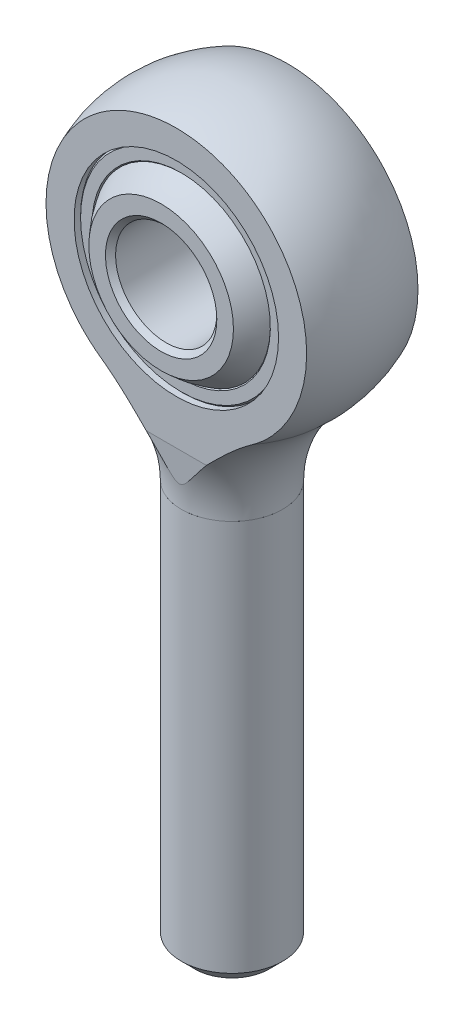
SolidWorks part; units mm, degrees
ref_plane "Front" through (0, 0, 0) normal (0, 0, 1) x (1, 0, 0)
ref_plane "Top" through (0, 0, 0) normal (0, 1, 0) x (1, 0, 0)
ref_plane "Right" through (0, 0, 0) normal (1, 0, 0) x (0, 0, -1)
sketch "Sketch1" plane through (0, 0, 0) normal (0, 0, 1) x (1, 0, 0)
  line L0 (0, 0) -> (0, -31.75)
  line L1 (0, -31.75) -> (3.9688, -31.75)
  line L2 (3.9688, -31.75) -> (3.9688, 0)
  line L3 (3.9688, 0) -> (0, 0)
  line L5 (0, 26.9875) -> (0, 0) construction
  line L6 (0, 26.9875) -> (11.1125, 26.9875) construction
  line L7 (11.1125, 26.9875) -> (11.1125, 15.875) construction
  line L8 (-3.9687, -31.75) -> (-3.9687, 0) construction
  arc A0 (7.3698, 7.558) -> (0, 26.9875) centre (0, 15.875) ccw construction
  circle A1 centre (0, 15.875) radius 3.9688 construction
  circle A2 centre (0, 15.875) radius 7.9375 construction
  circle A3 centre (0, 15.875) radius 8.0169 construction
  arc A4 (3.9688, 0) -> (7.3698, 7.558) centre (14.067, 0) cw construction
  point P16 (-3.9687, -24.6062)
  dimension "A" = 7.9375
  dimension "Ball Dia" = 15.875
  dimension "B" = 22.225
  dimension "D1" = 16.0337
  dimension "D" = 47.625
  dimension "E" = 31.75
  dimension "Thread Dia" = 7.9375
  dimension "D2" = 7.1438
revolve "Revolve1" add sketch "Sketch1" angle 360 about L5
sketch "Sketch12" [suppressed] plane through (0, -31.75, 0) normal (0, -1, 0) x (1, 0, 0)
  circle A1 centre (0, 0) radius 3.9688
  circle A2 centre (0, 0) radius 3.9688
  dimension "D1" = 0
chamfer "Chamfer2" distance 1.0583 angle 45 1 edges at (-3.9687, -31.75, 0)
sketch "Sketch4" plane through (0, 0, 0) normal (0, 0, 1) x (1, 0, 0)
  line L0 (3.9688, 0) -> (0, 0) construction
  line L2 (0, 26.9875) -> (0, 0) construction
  line L3 (3.9688, 0) -> (0, 0)
  line L5 (0, 26.9875) -> (0, 0)
  line L6 (0, 26.9875) -> (0, 29.5275) construction
  arc A0 (7.3698, 7.558) -> (0, 26.9875) centre (0, 15.875) ccw construction
  arc A1 (7.3698, 7.558) -> (0, 26.9875) centre (0, 15.875) ccw
  arc A2 (7.3698, 7.558) -> (3.9688, 0) centre (14.067, 0) ccw construction
  arc A3 (7.3698, 7.558) -> (3.9688, 0) centre (14.067, 0) ccw
  dimension "D1" = 2.54
revolve "Revolve2" add sketch "Sketch4" angle 360 about L6
sketch "Sketch5" plane through (0, 0, 0) normal (1, 0, 0) x (0, 0, -1)
  line L0 (4.3656, 26.9875) -> (11.1125, 26.9875)
  line L1 (-4.3656, 26.9875) -> (4.3656, 26.9875) construction
  line L2 (-4.3656, 26.9875) -> (-4.3656, 4.3656)
  line L3 (-3.9688, 0) -> (3.9688, 0) construction
  line L4 (4.3656, 26.9875) -> (4.3656, 4.3656)
  line L5 (11.1125, 26.9875) -> (11.1125, 0)
  line L6 (11.1125, 0) -> (3.9688, 0)
  line L7 (-3.9688, 0) -> (-11.1125, 0)
  line L8 (-11.1125, 0) -> (-11.1125, 26.9875)
  line L9 (-11.1125, 26.9875) -> (-4.3656, 26.9875)
  line L10 (3.9688, 0) -> (4.3656, 4.3656)
  line L11 (-3.9688, 0) -> (-4.3656, 4.3656)
  line L12 (-4.3656, 4.3656) -> (4.3656, 4.3656) construction
  line L13 (0, 0) -> (0, 4.3656) construction
  arc A0 (7.3698, 7.558) -> (-7.3698, 7.558) centre (0, 15.875) ccw construction
  dimension "F" = 8.7312
  dimension "D2" = 4.3656
  dimension "D1" = 7.9375
extrude "Cut-Extrude1" cut sketch "Sketch5" against normal through all and the other way through all
sketch "Sketch6" plane through (0, 0, 0) normal (0, 0, 1) x (1, 0, 0)
  circle A0 centre (0, 15.875) radius 8.0169 construction
  circle A1 centre (0, 15.875) radius 8.0169
extrude "Cut-Extrude2" cut sketch "Sketch6" against normal through all and the other way through all
sketch "Sketch7" plane through (0, 0, 0) normal (0, 0, 1) x (1, 0, 0)
  line L0 (0, 23.8125) -> (0, 7.9375)
  line L1 (0, 26.9875) -> (0, 0) construction
  line L2 (0, 0) -> (0, 7.9375) construction
  arc A0 (0, 7.9375) -> (0, 23.8125) centre (0, 15.875) ccw
  circle A1 centre (0, 15.875) radius 7.9375 construction
revolve "Revolve3" add sketch "Sketch7" angle 360 about L2
sketch "Sketch8" plane through (0, 0, 0) normal (1, 0, 0) x (0, 0, -1)
  line L0 (-4.3656, 26.9875) -> (4.3656, 26.9875) construction
  line L1 (-5.5562, 26.9875) -> (5.5562, 26.9875) construction
  line L2 (-5.5562, 26.9875) -> (-5.5563, 0)
  line L3 (-5.5563, 0) -> (5.5563, 0) construction
  line L4 (5.5562, 26.9875) -> (5.5563, 0)
  line L5 (5.5562, 26.9875) -> (11.1125, 26.9875)
  line L6 (11.1125, 26.9875) -> (11.1125, 0)
  line L7 (11.1125, 0) -> (5.5563, 0)
  line L8 (-5.5563, 0) -> (-11.1125, 0)
  line L9 (-11.1125, 0) -> (-11.1125, 26.9875)
  line L10 (-11.1125, 26.9875) -> (-5.5562, 26.9875)
  dimension "C" = 11.1125
extrude "Cut-Extrude3" cut sketch "Sketch8" against normal through all and the other way through all
sketch "Sketch10" plane through (0, 0, 0) normal (0, 0, 1) x (1, 0, 0)
  circle A0 centre (0, 15.875) radius 3.9688 construction
  circle A1 centre (0, 15.875) radius 3.9688
extrude "Cut-Extrude4" cut sketch "Sketch10" against normal through all and the other way through all
chamfer "Chamfer1" distance 0.3969 angle 45 2 edges at (3.9687, 15.875, -5.5562) (3.9687, 15.875, 5.5562)
sketch "Sketch14" plane through (0, 0, 0) normal (1, 0, 0) x (0, 0, -1)
  line L0 (-3.9846, 23.8919) -> (-3.9846, 22.7399)
  line L1 (-3.9846, 23.8919) -> (-1.6558, 23.8919)
  line L2 (-1.6558, 23.8919) -> (-1.6558, 23.6379)
  line L3 (3.9846, 22.7399) -> (3.9846, 23.8919)
  line L4 (3.9846, 23.8919) -> (1.6558, 23.8919)
  line L5 (1.6558, 23.8919) -> (1.6558, 23.6379)
  line L8 (-5.5562, 15.875) -> (5.5562, 15.875) construction
  line L9 (-5.5562, 21.5435) -> (-5.5562, 10.2065) construction
  line L10 (4.3656, 23.8919) -> (-4.3656, 23.8919) construction
  line L11 (-4.3656, 26.094) -> (-4.3656, 7.558) construction
  arc A1 (3.9846, 22.7399) -> (1.6558, 23.6379) centre (0, 15.875) ccw
  arc A2 (-1.6558, 23.6379) -> (-3.9846, 22.7399) centre (0, 15.875) ccw
  arc A3 (5.5562, 21.5435) -> (-5.5562, 21.5435) centre (0, 15.875) ccw construction
  dimension "D1" = 0.381
  dimension "D2" = 0.254
revolve "Revolve4" add sketch "Sketch14" angle 360 about L8
chamfer "Chamfer3" distance 0.127 angle 45 2 edges at (0, 7.8581, 3.9846) (0, 9.0101, 3.9846) first distance on face at (0, 7.8581, 3.9846) first distance on face at (0, 9.0101, 3.9846)
chamfer "Chamfer4" distance 0.127 angle 45 2 edges at (0, 9.0101, -3.9846) (0, 7.8581, -3.9846) first distance on face at (0, 9.0101, -3.9846) first distance on face at (0, 7.8581, -3.9846)
sketch "Sketch11" plane through (0, 0, 0) normal (1, 0, 0) x (0, 0, -1)
  line L0 (0, 15.875) -> (-5.5563, 16.5572) construction
  line L1 (4.3656, 15.875) -> (-4.3656, 15.875) construction
  line L2 (0, 15.875) -> (-5.5563, 15.1928) construction
  line L3 (0, 26.9875) -> (0, 0) construction
  line L4 (-5.5562, 26.9875) -> (-5.5563, 0) construction
  line L5 (0, 15.875) -> (0.0074, 15.875) construction
  dimension "Swivel" = 14
curve "Helix/Spiral1" [suppressed] pitch 1.0583 height 33.1248 turns 31.299 parameters "pitch"=1.0583
sketch "Sketch13" [suppressed] plane through (0, 0, 0) normal (1, 0, 0) x (0, 0, -1)
  line L0 (-3.9688, -32.676) -> (-3.9688, -31.75)
  line L1 (-3.9688, -31.75) -> (-3.2813, -32.1469)
  line L2 (-3.2813, -32.1469) -> (-3.2813, -32.2792)
  line L3 (-3.2813, -32.2792) -> (-3.9688, -32.676)
  line L4 (-3.2813, -32.213) -> (-3.9688, -32.213) construction
  line L5 (-3.625, -32.4776) -> (-3.625, -31.9484) construction
  line L6 (-3.9688, -31.75) -> (3.9688, -31.75) construction
  dimension "D1" = 0.1323
  dimension "D2" = 0.5292
  dimension "D3" = 60
sweep "Cut-Sweep1" [suppressed] cut profiles "Sketch13" path "Helix/Spiral1"
sketch "Sketch15" [suppressed] plane through (0, 0, 0) normal (0, -1, 0) x (1, 0, 0)
  arc A2 (0, -3.9688) -> (0, 3.9688) centre (0, 0) ccw
  arc A3 (0, 3.9688) -> (0, -3.9688) centre (0, 0) ccw
  arc A5 (0, 3.9688) -> (0, -3.9688) centre (0, 0) ccw
  arc A6 (0, -3.9688) -> (0, 3.9688) centre (0, 0) ccw
  dimension "D1" = 0
extrude "Boss-Extrude1" [suppressed] add sketch "Sketch15" along normal up to next draft 20
ref_axis "Center Axis 1" through (0, 15.875, -1.6345) along (0, 0, 1)
ref_axis "Center Axis 2" [suppressed] through (0, 29.9244, 0) along (0, -1, 0)
ref_axis "Axis1" through (0, 0, 0) along (0, -1, 0)
ref_point "Point2"
equation "\"D1@Sketch1\"=\"Ball Dia@Sketch1\"*1.01"
equation "\"D1@Chamfer1\"=\"A@Sketch1\"/20"
equation "\"D1@Sketch5\"=\"Thread Dia@Sketch1\""
equation "\"D2@Sketch5\"=\"F@Sketch5\"/2"
equation "\"D1@Sketch13\" = \"pitch@Helix/Spiral1\"*.125"
equation "\"D2@Sketch13\" = \"pitch@Helix/Spiral1\"*.50"
equation "\"D1@Chamfer2\" = \"pitch@Helix/Spiral1\""
equation "\"D2@Sketch1\" = \"pitch@Helix/Spiral1\"*6.750"
equation "\"D3@Helix/Spiral1\"=\"E@Sketch1\"+\"pitch@Helix/Spiral1\"+.0124578"
